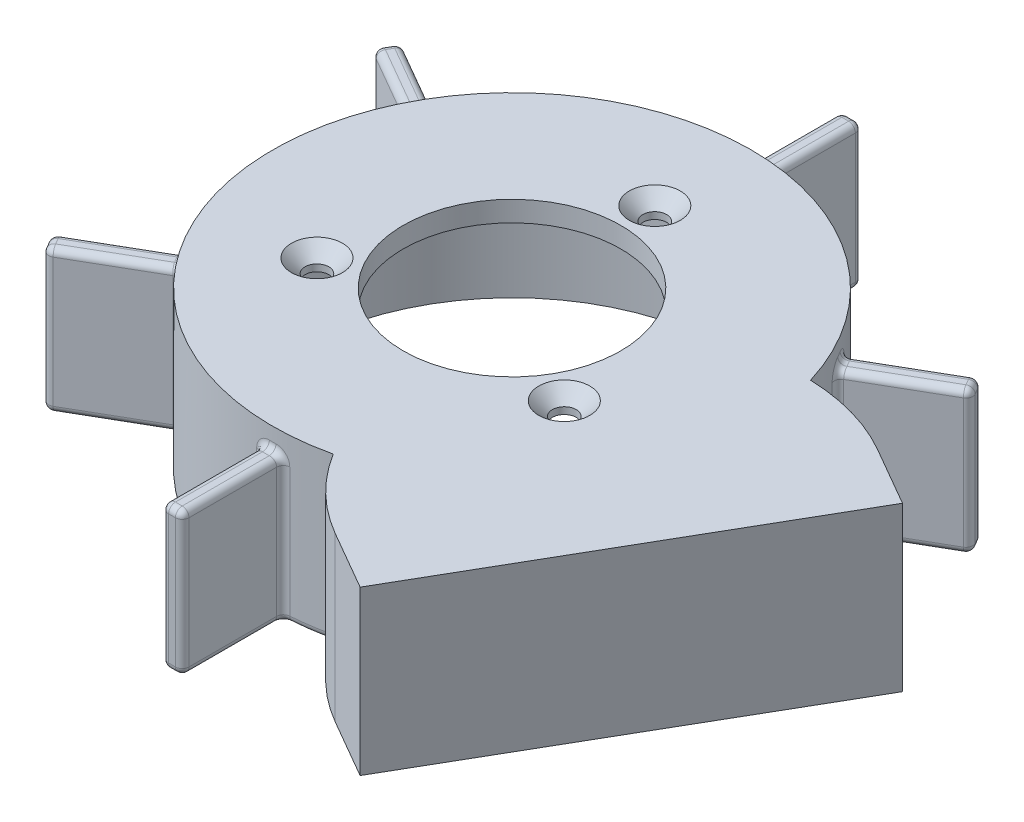
SolidWorks part; units mm, degrees
ref_plane "Front Plane" through (0, 0, 0) normal (0, 0, 1) x (1, 0, 0)
ref_plane "Top Plane" through (0, 0, 0) normal (0, 1, 0) x (1, 0, 0)
ref_plane "Right Plane" through (0, 0, 0) normal (1, 0, 0) x (0, 0, -1)
sketch "Sketch1" plane through (0, 0, 0) normal (0, 1, 0) x (1, 0, 0)
  circle A0 centre (0, 0) radius 17.6
  circle A2 centre (0, 0) radius 8
  circle A3 centre (0, 10.5) radius 0.875
  circle A7 centre (9.0948, -5.2491) radius 0.875
  circle A9 centre (-9.0918, -5.2509) radius 0.875
  point P14 (0, 0)
  point P23 (0.001, 0)
  dimension "D1" = 35.2
  dimension "D3" = 16
  dimension "D4" = 1.75
  dimension "D6" = 3
extrude "Boss-Extrude2" add sketch "Sketch1" along normal blind 1.5
chamfer "Chamfer1" distance 1 angle 45 3 edges at (9.0948, 1.5, 6.1241) (-9.0918, 1.5, 6.1259) (0, 1.5, -9.625)
sketch "Sketch2" plane through (0, 0, 0) normal (0, -1, 0) x (1, 0, 0)
  line L4 (22.0256, -11.8505) -> (21.2756, -13.1495)
  line L5 (-0.75, -25) -> (0.75, -25)
  line L6 (-0.75, -25) -> (-0.75, 25)
  line L7 (-0.75, 25) -> (0.75, 25)
  line L8 (0.75, -25) -> (0.75, 25)
  line L9 (-0.75, -25) -> (0.75, 25) construction
  line L10 (-0.75, 25) -> (0.75, -25) construction
  line L11 (-22.0256, 11.8505) -> (21.2756, -13.1495)
  line L12 (-21.2756, 13.1495) -> (22.0256, -11.8505)
  line L13 (-21.2756, 13.1495) -> (-22.0256, 11.8505)
  line L14 (-21.2756, -13.1495) -> (-22.0256, -11.8505)
  line L15 (21.2756, 13.1495) -> (-22.0256, -11.8505)
  line L16 (22.0256, 11.8505) -> (-21.2756, -13.1495)
  line L17 (22.0256, 11.8505) -> (21.2756, 13.1495)
  circle A0 centre (0, 0) radius 16.1
  circle A1 centre (0, 0) radius 17.6
  point P7 (-22.903, 10.7941)
  point P19 (0, 0)
  circle M4 centre (0, 0) radius 17.6
  dimension "D1" = 32.2
  dimension "D2" = 1.5
  dimension "D3" = 50
  dimension "D4" = 3
extrude "Boss-Extrude3" add sketch "Sketch2" along normal blind 10.5 contours A0 L6 L12 M4 | A0 L8 L6 M4 | A0 L15 L8 M4 | L8 L7 L6 M4 | A0 L12 L11 M4 | L12 L13 L11 M4 | A0 L11 L15 M4 | L16 L15 L14 M4 | A0 L15 L16 M4 | A0 L16 L6 M4 | L5 L8 L6 M4 | A0 L6 L8 M4 | A0 L8 L11 M4 | A0 L11 L12 M4 | L12 L11 L4 M4 | A0 L12 L16 M4 | A0 L16 L15 M4 region at (18.444, 0, -10.6487) region at (14.5877, 0, -8.4222) region at (16.2244, 0, 0) region at (8.1122, 0, -14.0508) region at (0, 0, -16.8444) region at (0, 0, -21.2973) region at (14.5877, 0, 8.4222) region at (-8.1122, 0, -14.0508) region at (8.1122, 0, 14.0508) region at (-14.5877, 0, -8.4222) region at (-18.444, 0, -10.6487) region at (0, 0, 21.2973) region at (0, 0, 16.8444) region at (-16.2244, 0, 0) region at (-8.1122, 0, 14.0508) region at (-14.5877, 0, 8.4222) region at (-18.444, 0, 10.6487)
fillet "Fillet3" radius 0.5 60 edges at (0.75, -10.5, -21.292) (0, -10.5, -25) (-0.75, -10.5, -21.292) (-8.8, -10.5, -15.242) (-17.6, -10.5, 0) (-18.8144, -10.5, 9.9965) (-21.6506, -10.5, 12.5) (-18.0644, -10.5, 11.2955) (-8.8, -10.5, 15.242) (-0.75, -10.5, 21.292) (0, -10.5, 25) (0.75, -10.5, 21.292) (15.242, -10.5, 8.8) (-18.8144, -10.5, -9.9965) (-18.0644, -10.5, -11.2955) (18.8144, -10.5, -9.9965) (21.6506, -10.5, -12.5) (18.0644, -10.5, -11.2955) (8.8, -10.5, -15.242) (-15.6032, -5.25, -8.1425) (-22.0256, -5.25, -11.8505) (-21.6506, -10.5, -12.5) (-18.8144, 0, -9.9965) (-21.6506, 0, -12.5) (-15.242, 0, -8.8) (-21.2756, -5.25, -13.1495) (-14.8532, -5.25, -9.4415) (-18.0644, 0, -11.2955) (14.8532, -5.25, -9.4415) (-15.6032, -5.25, 8.1425) (-18.8144, 0, 9.9965) (-15.242, 0, 8.8) (-22.0256, -5.25, 11.8505) (-21.6506, 0, 12.5) (-14.8532, -5.25, 9.4415) (-21.2756, -5.25, 13.1495) (-18.0644, 0, 11.2955) (0.75, -5.25, 17.584) (-0.75, -5.25, 17.584) (0.75, -5.25, 25) (-0.75, -5.25, 25) (0.75, 0, 21.292) (0, 0, 25) (-0.75, 0, 21.292) (0, 0, 17.6) (15.6032, -5.25, -8.1425) (21.2756, -5.25, -13.1495) (22.0256, -5.25, -11.8505) (18.0644, 0, -11.2955) (21.6506, 0, -12.5) (18.8144, 0, -9.9965) (15.242, 0, -8.8) (-0.75, -5.25, -17.584) (-0.75, -5.25, -25) (-0.75, 0, -21.292) (0, 0, -25) (0, 0, -17.6) (0.75, -5.25, -25) (0.75, -5.25, -17.584) (0.75, 0, -21.292)
sketch "Sketch3" plane through (0, 1.5, 0) normal (0, 1, 0) x (1, 0, 0)
  line L0 (1.2155, -17.558) -> (15.8134, 7.7264)
  line L1 (1.2155, -17.558) -> (9.129, -22.1269)
  line L2 (15.8134, 7.7264) -> (23.727, 3.1575)
  line L3 (9.129, -22.1269) -> (23.727, 3.1575)
  line L4 (1.2155, -17.558) -> (9.129, -22.1269)
  line L5 (1.2155, -17.558) -> (3.7155, -13.2279)
  line L6 (9.129, -22.1269) -> (11.629, -17.7968)
  line L7 (3.7155, -13.2279) -> (11.629, -17.7968)
  line L8 (15.8134, 7.7264) -> (23.727, 3.1575)
  line L9 (15.8134, 7.7264) -> (13.3134, 3.3962)
  line L10 (23.727, 3.1575) -> (21.227, -1.1727)
  line L11 (13.3134, 3.3962) -> (21.227, -1.1727)
  line L12 (23.727, 3.1575) -> (9.129, -22.1269)
  line L13 (23.727, 3.1575) -> (28.0571, 0.6575)
  line L14 (9.129, -22.1269) -> (13.4592, -24.6269)
  line L15 (28.0571, 0.6575) -> (13.4592, -24.6269)
  circle A0 centre (16.428, -9.4847) radius 14.5979
  circle M9 centre (0, 0) radius 17.6
  dimension "D1" = 5
  dimension "D2" = 5
  dimension "D3" = 5
extrude "Boss-Extrude4" add sketch "Sketch3" against normal up to surface (12 mm away) contours L3 A0 L11 M9 | L11 L7 L3 M9 | A0 L3 L7 M9 | L15 A0 L3 | A0 L15 L13 | A0 L14 L15 region at (15.3054, 1.5, 8.8366) region at (8.0334, 1.5, 18.5515) region at (20.0828, 1.5, -2.3187) region at (18.5709, 1.5, 10.7219) region at (12.515, 1.5, 23.7776) region at (26.8495, 1.5, -1.0505) up to face at (-3.3002, -10.5, -1.9054)
sketch "Sketch4" plane through (0, -10.5, 0) normal (0, -1, 0) x (1, 0, 0)
  line L0 (9.129, 22.1269) -> (23.727, -3.1575) construction
  line L1 (9.129, 22.1269) -> (23.727, -3.1575)
  line L2 (9.129, 22.1269) -> (7.397, 21.1269)
  line L3 (23.727, -3.1575) -> (21.9949, -4.1575)
  line L4 (7.397, 21.1269) -> (21.9949, -4.1575)
  circle A0 centre (16.428, 9.4847) radius 14.5979
  circle A1 centre (16.428, 9.4847) radius 12.5
  dimension "D1" = 25
  dimension "D2" = 2
extrude "Cut-Extrude1" cut sketch "Sketch4" against normal up to surface (10.5 mm away) contours L4 A1 | L4 A1 L1 region at (15.5638, -10.5, 8.9858) region at (10.8844, -10.5, 6.2841) up to face at (-9.0918, 0, 6.1259)
